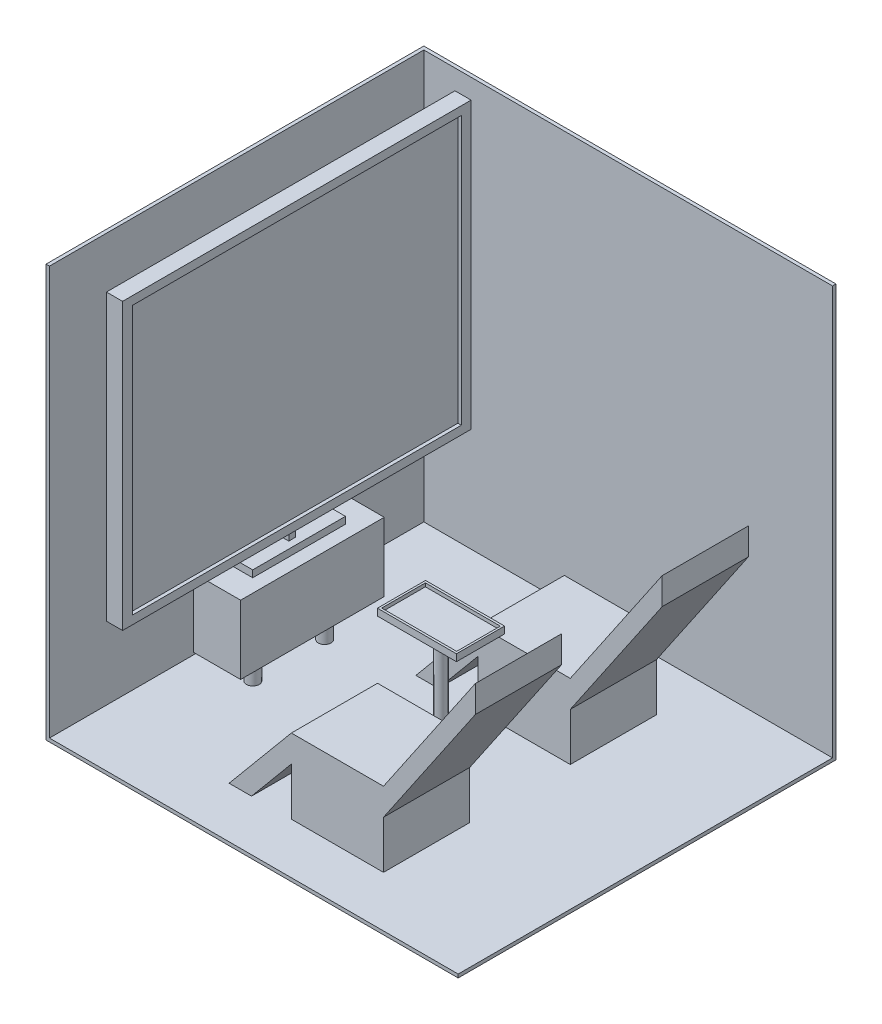
SolidWorks part; units mm, degrees
ref_plane "정면" through (0, 0, 0) normal (0, 0, 1) x (1, 0, 0)
ref_plane "윗면" through (0, 0, 0) normal (0, 1, 0) x (1, 0, 0)
ref_plane "우측면" through (0, 0, 0) normal (1, 0, 0) x (0, 0, -1)
sketch "스케치1" plane through (0, 0, 0) normal (0, 1, 0) x (1, 0, 0)
  line L1 (-60, 55) -> (60, 55)
  line L2 (-60, 55) -> (-60, -55)
  line L3 (-60, -55) -> (60, -55)
  line L4 (60, 55) -> (60, -55)
  line L5 (-60, 55) -> (60, -55) construction
  line L6 (-60, -55) -> (60, 55) construction
  point P0 (0, 0)
  dimension "D1" = 120
  dimension "D2" = 110
extrude "보스-돌출1" add sketch "스케치1" along normal blind 120
sketch "스케치2" plane through (0, 0, 55) normal (0, 0, 1) x (1, 0, 0)
  line L1 (60, 120) -> (-59, 120)
  line L2 (60, 120) -> (60, 1)
  line L3 (60, 1) -> (-59, 1)
  line L4 (-59, 120) -> (-59, 1)
  dimension "D1" = 119
  dimension "D2" = 119
extrude "컷-돌출1" cut sketch "스케치2" against normal blind 109
sketch "스케치3" plane through (0, 1, 0) normal (0, 1, 0) x (1, 0, 0)
  line L0 (-43.822, -55) -> (-43.822, 54) construction
  line L1 (-59, -55) -> (60, -55) construction
  line L2 (-59, 54) -> (60, 54) construction
  line L3 (-50.7068, -0.5) -> (-36.9373, -0.5) construction
  line L4 (-50.7068, 20.4082) -> (-36.9373, 20.4082)
  line L5 (-50.7068, 20.4082) -> (-50.7068, -21.4082)
  line L6 (-50.7068, -21.4082) -> (-36.9373, -21.4082)
  line L7 (-36.9373, 20.4082) -> (-36.9373, -21.4082)
  line L8 (-50.7068, 20.4082) -> (-36.9373, -21.4082) construction
  line L9 (-50.7068, -21.4082) -> (-36.9373, 20.4082) construction
  point P6 (-43.822, -0.5)
extrude "보스-돌출2" add sketch "스케치3" along normal blind 29
extrude "컷-돌출2" cut sketch "스케치3<2>" along normal blind 9
sketch "스케치3<2>" plane through (0, 1, 0) normal (0, 1, 0) x (1, 0, 0) same geometry as "스케치3"
sketch "스케치6" plane through (0, 1, 0) normal (0, 1, 0) x (1, 0, 0)
  line L0 (-36.9373, -0.5) -> (-50.7068, -0.5) construction
  line L1 (-50.7068, 20.4082) -> (-36.9373, 20.4082)
  line L2 (-50.7068, 20.4082) -> (-50.7068, -21.4082)
  line L3 (-50.7068, -21.4082) -> (-36.9373, -21.4082)
  line L4 (-36.9373, 20.4082) -> (-36.9373, -21.4082)
  line L5 (-43.822, 20.4082) -> (-43.822, -0.5) construction
  circle A0 centre (-43.822, 9.9541) radius 1.8569
  circle A1 centre (-43.822, -10.9541) radius 1.8569
extrude "보스-돌출4" add sketch "스케치6" along normal blind 9 contours A1 | A0 region at (-43.822, 1, 10.9541)
sketch "스케치7" plane through (0, 30, 0) normal (0, 1, 0) x (1, 0, 0)
  line L0 (-50.7068, -0.5) -> (-36.9373, -0.5) construction
  line L1 (-50.7068, 20.4082) -> (-36.9373, 20.4082) construction
  line L2 (-50.7068, 20.4082) -> (-50.7068, -21.4082) construction
  line L3 (-50.7068, -21.4082) -> (-36.9373, -21.4082) construction
  line L4 (-36.9373, 20.4082) -> (-36.9373, -21.4082) construction
  line L6 (-46.822, 13) -> (-40.822, 13)
  line L7 (-46.822, 13) -> (-46.822, -14)
  line L8 (-46.822, -14) -> (-40.822, -14)
  line L9 (-40.822, 13) -> (-40.822, -14)
  line L10 (-46.822, 13) -> (-40.822, -14) construction
  line L11 (-46.822, -14) -> (-40.822, 13) construction
  point P8 (-43.822, -0.5)
  dimension "D1" = 6
  dimension "D2" = 27
extrude "보스-돌출5" add sketch "스케치7" along normal blind 2 separate body
sketch "스케치8" plane through (0, 32, 0) normal (0, 1, 0) x (1, 0, 0)
  line L0 (-43.822, 13) -> (-43.822, -14) construction
  line L1 (-40.822, 13) -> (-46.822, 13) construction
  line L2 (-46.822, -14) -> (-40.822, -14) construction
  line L4 (-44.822, 0.5) -> (-42.822, 0.5)
  line L5 (-44.822, 0.5) -> (-44.822, -1.5)
  line L6 (-44.822, -1.5) -> (-42.822, -1.5)
  line L7 (-42.822, 0.5) -> (-42.822, -1.5)
  line L8 (-44.822, 0.5) -> (-42.822, -1.5) construction
  line L9 (-44.822, -1.5) -> (-42.822, 0.5) construction
  point P6 (-43.822, -0.5)
  dimension "D1" = 2
  dimension "D2" = 2
extrude "보스-돌출6" add sketch "스케치8" along normal blind 3
sketch "스케치9" plane through (0, 35, 0) normal (0, 1, 0) x (1, 0, 0)
  line L0 (-43.822, -1.5) -> (-43.822, 0.5) construction
  line L1 (-44.822, -1.5) -> (-42.822, -1.5) construction
  line L2 (-42.822, 0.5) -> (-44.822, 0.5) construction
  line L4 (-46.1676, 50.2361) -> (-41.4765, 50.2361)
  line L5 (-46.1676, 50.2361) -> (-46.1676, -51.2361)
  line L6 (-46.1676, -51.2361) -> (-41.4765, -51.2361)
  line L7 (-41.4765, 50.2361) -> (-41.4765, -51.2361)
  line L8 (-46.1676, 50.2361) -> (-41.4765, -51.2361) construction
  line L9 (-46.1676, -51.2361) -> (-41.4765, 50.2361) construction
  point P6 (-43.822, -0.5)
extrude "보스-돌출7" add sketch "스케치9" along normal blind 83
sketch "스케치10" plane through (-41.4765, 0, 0) normal (1, 0, 0) x (0, 0, -1)
  line L0 (-0.5, 118) -> (-0.5, 35) construction
  line L1 (-51.2361, 118) -> (50.2361, 118) construction
  line L2 (-51.2361, 35) -> (50.2361, 35) construction
  line L4 (-48.388, 115.5491) -> (47.388, 115.5491)
  line L5 (-48.388, 115.5491) -> (-48.388, 37.4509)
  line L6 (-48.388, 37.4509) -> (47.388, 37.4509)
  line L7 (47.388, 115.5491) -> (47.388, 37.4509)
  line L8 (-48.388, 115.5491) -> (47.388, 37.4509) construction
  line L9 (-48.388, 37.4509) -> (47.388, 115.5491) construction
  point P6 (-0.5, 76.5)
extrude "컷-돌출3" cut sketch "스케치10" against normal blind 1
sketch "스케치11" plane through (0, 1, 0) normal (0, 1, 0) x (1, 0, 0)
  line L0 (60, -0.5) -> (-59, -0.5) construction
  line L1 (60, 54) -> (60, -55) construction
  line L2 (-59, 54) -> (-59, -55) construction
  line L3 (50.2453, -40.2384) -> (50.2453, -15.1436)
  line L4 (50.2453, 39.2384) -> (-21.4542, 39.2384)
  line L5 (50.2453, 39.2384) -> (50.2453, 14.1436)
  line L6 (50.2453, 14.1436) -> (-21.4542, 14.1436)
  line L7 (-21.4542, 39.2384) -> (-21.4542, 14.1436)
  line L8 (50.2453, -40.2384) -> (-21.4542, -40.2384)
  line L9 (-21.4542, -40.2384) -> (-21.4542, -15.1436)
  line L10 (50.2453, -15.1436) -> (-21.4542, -15.1436)
extrude "보스-돌출9" add sketch "스케치11" along normal blind 61
sketch "스케치12" plane through (0, 0, 40.2384) normal (0, 0, 1) x (1, 0, 0)
  line L0 (-21.4542, 1) -> (-3.3297, 22.7251)
  line L1 (-3.3297, 22.7251) -> (23.4975, 22.7251)
  line L2 (23.4975, 22.7251) -> (50.2453, 62)
  line L3 (-21.4542, 62) -> (50.2453, 62) construction
  line L4 (50.2453, 62) -> (50.2453, 54.1831)
  line L5 (50.2453, 62) -> (50.2453, 1) construction
  line L6 (50.2453, 54.1831) -> (23.4975, 14.9082)
  line L7 (23.4975, 14.9082) -> (23.4975, 1)
  line L8 (-21.4542, 1) -> (50.2453, 1) construction
  line L9 (23.4975, 1) -> (-3.3297, 1)
  line L10 (-3.3297, 1) -> (-3.3297, 14.9082)
  line L11 (-3.3297, 14.9082) -> (-14.9329, 1)
  line L12 (-14.9329, 1) -> (-21.4542, 1)
  line L13 (-21.4542, 1) -> (-21.4542, 62)
  line L14 (-21.4542, 62) -> (50.2453, 62)
  line L15 (50.2453, 54.1831) -> (50.2453, 1)
  line L16 (-59, 1) -> (60, 1) construction
  line L17 (50.2453, 1) -> (23.4975, 1)
  line M11 (-21.4542, 1) -> (50.2453, 1)
  line M12 (50.2453, 1) -> (50.2453, 62)
  line M13 (50.2453, 62) -> (-21.4542, 62)
  line M14 (-21.4542, 62) -> (-21.4542, 1)
extrude "컷-돌출4" cut sketch "스케치12" against normal blind 81 contours L1 L2 L0 M13 M14 | L6 L7 M11 M12 | L10 L11 M11 region at (6.3493, 41.6174, 40.2384) region at (-7.1974, 5.6361, 40.2384) region at (39.4811, 19.6888, 40.2384)
sketch "스케치13" plane through (0, 1, 0) normal (0, 1, 0) x (1, 0, 0)
  line L0 (60, -0.5) -> (-59, -0.5) construction
  line L1 (60, 54) -> (60, -55) construction
  line L2 (-59, 54) -> (-59, -55) construction
  circle A0 centre (0.5, -0.5) radius 1.5
extrude "보스-돌출10" add sketch "스케치13" along normal blind 31
sketch "스케치14" plane through (0, 32, 0) normal (0, 1, 0) x (1, 0, 0)
  line L1 (-11, 6.5) -> (12, 6.5)
  line L2 (-11, 6.5) -> (-11, -7.5)
  line L3 (-11, -7.5) -> (12, -7.5)
  line L4 (12, 6.5) -> (12, -7.5)
  line L5 (-11, 6.5) -> (12, -7.5) construction
  line L6 (-11, -7.5) -> (12, 6.5) construction
  point P0 (0.5, -0.5)
  dimension "D1" = 23
  dimension "D2" = 14
extrude "보스-돌출11" add sketch "스케치14" along normal blind 2
sketch "스케치15" plane through (0, 34, 0) normal (0, 1, 0) x (1, 0, 0)
  line L0 (-11, -0.5) -> (12, -0.5) construction
  line L1 (-11, 6.5) -> (-11, -7.5) construction
  line L2 (12, -7.5) -> (12, 6.5) construction
  line L4 (-10.415, 5.8614) -> (11.415, 5.8614)
  line L5 (-10.415, 5.8614) -> (-10.415, -6.8614)
  line L6 (-10.415, -6.8614) -> (11.415, -6.8614)
  line L7 (11.415, 5.8614) -> (11.415, -6.8614)
  line L8 (-10.415, 5.8614) -> (11.415, -6.8614) construction
  line L9 (-10.415, -6.8614) -> (11.415, 5.8614) construction
  point P6 (0.5, -0.5)
extrude "컷-돌출5" cut sketch "스케치15" against normal blind 1
